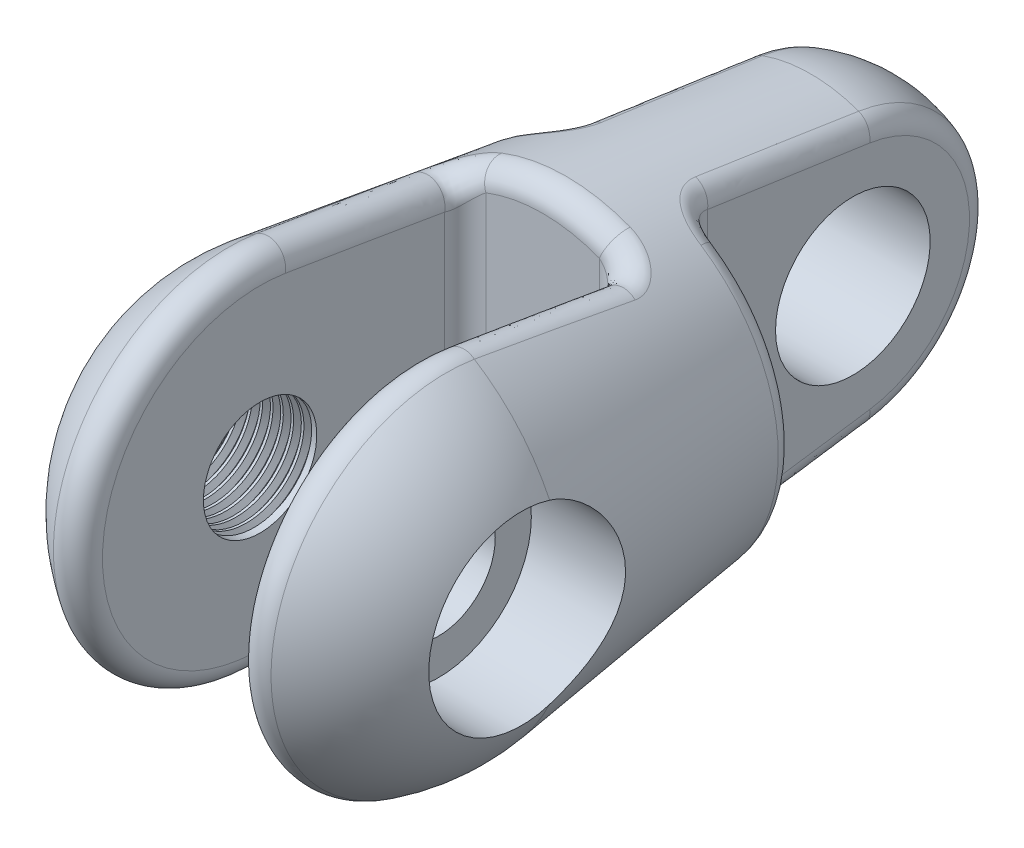
SolidWorks part; units mm, degrees
ref_plane "Front Plane" through (0, 0, 0) normal (0, 0, 1) x (1, 0, 0)
ref_plane "Top Plane" through (0, 0, 0) normal (0, 1, 0) x (1, 0, 0)
ref_plane "Right Plane" through (0, 0, 0) normal (1, 0, 0) x (0, 0, -1)
sketch "Sketch1" plane through (0, 0, 0) normal (0, 1, 0) x (1, 0, 0)
  line L0 (-5.5615, -150.4527) -> (0, 0) construction
  circle A1 centre (0, 0) radius 50.1285
  circle A2 centre (-5.5615, -150.4527) radius 59.9712
sketch "Sketch2" plane through (0, 0, 0) normal (0, 1, 0) x (1, 0, 0)
  line L0 (0, 14) -> (0, -64)
  line L1 (13.8692, 1.9091) -> (19.8132, -41.2727)
  arc A0 (0, -14) -> (0, 14) centre (0, 0) ccw
  arc A1 (0, -64) -> (0, -24) centre (0, -44) ccw
  dimension "D1" = 28
  dimension "D2" = 40
  dimension "D3" = 44
revolve "Revolve1" add sketch "Sketch2" angle 360 about L0 region at (5.9418, 0, 0) region at (10.3257, 0, 19.2067) region at (8.4883, 0, 44)
sketch "Sketch3" plane through (0, 0, 0) normal (0, 1, 0) x (1, 0, 0)
  line L0 (0, 0) -> (0, 21.1453) construction
  line L1 (0, 0) -> (0, -76.6685) construction
  line L2 (6, 1.9091) -> (6, -16.0909)
  line L3 (-13.8692, 1.9091) -> (13.8692, 1.9091) construction
  line L5 (6, -16.0909) -> (16.3469, -16.0909)
  line L7 (-19.8132, -41.2727) -> (-16.3469, -16.0909)
  line L8 (19.8132, -41.2727) -> (13.8692, 1.9091) construction
  line L9 (19.8132, -41.2727) -> (16.3469, -16.0909)
  line L10 (-6, 1.9091) -> (-6, -16.0909)
  line L11 (-6, -16.0909) -> (-16.3469, -16.0909)
  line L12 (6, 1.9091) -> (6, 12.6491)
  line L13 (-6, 1.9091) -> (-6, 12.6491)
  arc A0 (-19.8132, -41.2727) -> (19.8132, -41.2727) centre (0, -44) ccw construction
  arc A1 (-19.8132, -41.2727) -> (19.8132, -41.2727) centre (0, -44) ccw
  arc A2 (13.8692, 1.9091) -> (-13.8692, 1.9091) centre (0, 0) ccw construction
  arc A3 (6, 12.6491) -> (-6, 12.6491) centre (0, 0) ccw
  point P15 (0, 1.9091)
  dimension "D1" = 6
  dimension "D2" = 18
extrude "Cut-Extrude1" cut sketch "Sketch3" along normal mid plane 40 flip side to cut
sketch "Sketch4" plane through (-6, 0, 0) normal (-1, 0, 0) x (0, 0, 1)
  circle A0 centre (0, 0) radius 7.5
  dimension "D1" = 15
extrude "Cut-Extrude2" cut sketch "Sketch4" against normal through all
sketch "Sketch5" plane through (0, 0, 0) normal (0, 1, 0) x (1, 0, 0)
  line L0 (0, 1.9091) -> (0, -73.996) construction
  line L1 (-6, 1.9091) -> (6, 1.9091) construction
  line L2 (0, 1.9091) -> (0, -24.0909)
  line L4 (-7.5, -104.3009) -> (7.5, -104.3009)
  line L5 (-7.5, -104.3009) -> (-7.5, -24.0909)
  line L6 (-7.5, -24.0909) -> (7.5, -24.0909)
  line L7 (7.5, -104.3009) -> (7.5, -24.0909)
  line L8 (-7.5, -104.3009) -> (7.5, -24.0909) construction
  line L9 (-7.5, -24.0909) -> (7.5, -104.3009) construction
  point P5 (0, -64.1959)
  point P11 (0, 0)
  dimension "D1" = 26
  dimension "D2" = 15
extrude "Cut-Extrude3" cut sketch "Sketch5" against normal through all and the other way through all contours L4 L7 L6 L5 region at (0, 0, 64.1959)
sketch "Sketch8" plane through (0, 0, 16.0909) normal (0, 0, -1) x (-1, 0, 0)
  line L0 (-19.8132, 0) -> (-19.8132, 14.7539)
  arc A0 (-7.5, 18.3388) -> (-7.5, -18.3388) centre (0, 0) ccw construction
ref_plane "Plane1" through (19.8132, 0, 0) normal (-1, 0, 0) x (0, 1, 0)
hole_wizard "CBORE for M10 SHCS1" positions "Sketch10" profile "Sketch11" counterbore size "M10" standard "ANSI Metric" end condition through all
sketch "Sketch10" plane through (19.8132, 0, 0) normal (-1, 0, 0) x (0, 1, 0)
  point P0 (0, -44)
sketch "Sketch11" plane through (19.8132, 0, 44) normal (0, 1, 0) x (0, 0, -1)
  line L0 (0, 0) -> (0, 39.8132)
  line L1 (0, 39.8132) -> (5.5, 39.8132)
  line L3 (5.5, 39.8132) -> (5.5, 10)
  line L4 (5.5, 10) -> (9, 10)
  line L5 (9, 10) -> (9, 0)
  line L7 (9, 0) -> (0, 0)
  line L11 (0, -6.35) -> (0, 107.95) construction
  dimension "Thru Hole Dia." = 11
  dimension "Thru Hole Depth" = 39.8132
  dimension "C'Bore Dia." = 18
  dimension "C'Bore Depth" = 10
thread "Thread1" pitch 1 method cut profile "Thread Profile1" start angle 0, offset 0, length 0, pitch 1, diameter 11
ref_plane "Plane2" through (-7.5, 0, 49.5) normal (0, -1, 0) x (0, 0, 1)
sketch "Thread Profile1" plane through (-7.5, 0, 49.5) normal (0, -1, 0) x (0, 0, 1)
  line L0 (0, 0) -> (0, 1) construction
  line L1 (0, 0) -> (0.5413, 0.3125)
  line L2 (0.5413, 0.3125) -> (0.5413, 0.4375)
  line L3 (0.5413, 0.4375) -> (0, 0.75)
  line L4 (0.5413, 0.375) -> (0, 0.375) construction
  line L11 (0, 0) -> (0, 0.75)
  point P2 (0, 0)
  dimension "Pitch" = 1
  dimension "Profile_Angle" = 60
  dimension "Profile_Land" = 0.125
  dimension "Profile_Height" = 0.5413
fillet "Fillet1" radius 2 20 edges at (-6, 0, -12.6491) (6, 0, -12.6491) (7.5, 0, 62.5405) (-7.5, 0, 62.5405) (-7.5, 0, 24.0909) (7.5, 0, 24.0909) (0, -17.4481, 24.0909) (0, 17.4481, 24.0909) (6, 0, 16.0909) (16.3469, 0, 16.0909) (-16.3469, 0, 16.0909) (-6, 0, 16.0909)
